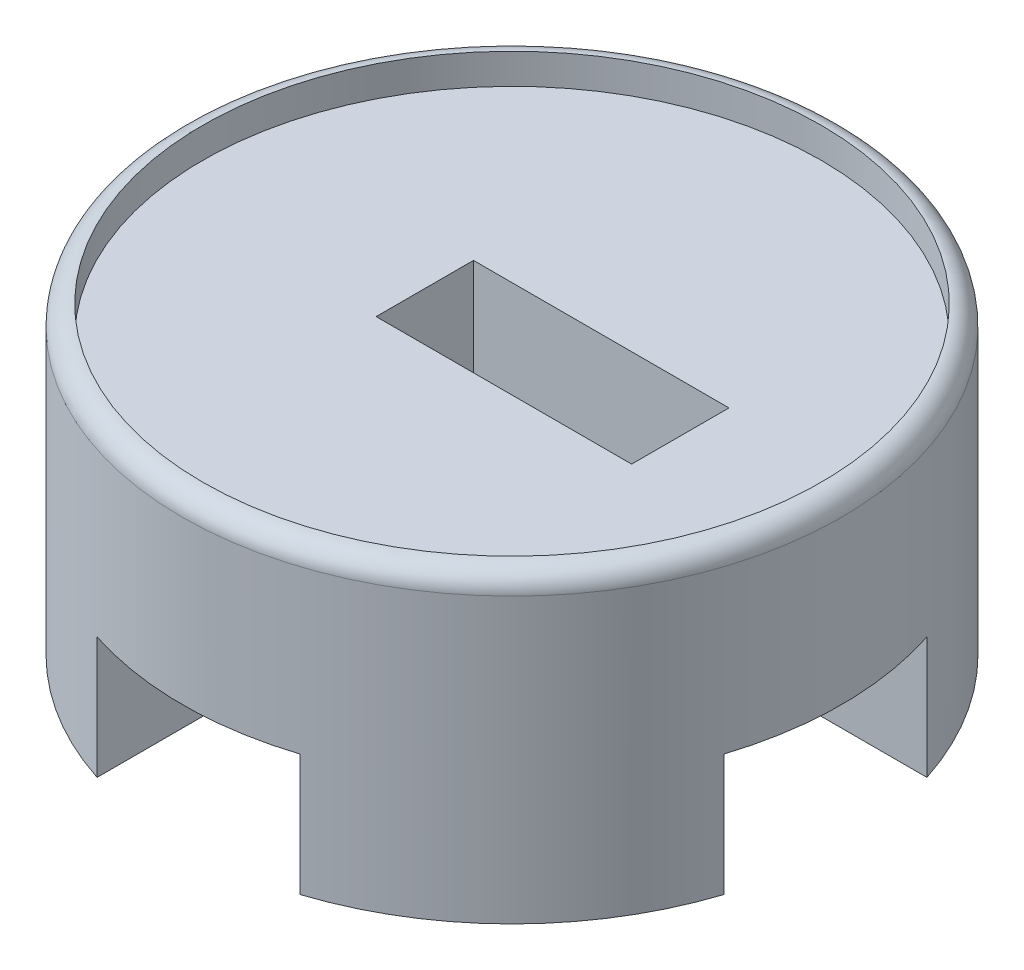
SolidWorks part; units mm, degrees
ref_plane "Front Plane" through (0, 0, 0) normal (0, 0, 1) x (1, 0, 0)
ref_plane "Top Plane" through (0, 0, 0) normal (0, 1, 0) x (1, 0, 0)
ref_plane "Right Plane" through (0, 0, 0) normal (1, 0, 0) x (0, 0, -1)
sketch "Sketch2" plane through (0, 0, 0) normal (0, 1, 0) x (1, 0, 0)
  circle A0 centre (0, 0) radius 41.275
  dimension "D1" = 82.55
extrude "Boss-Extrude2" add sketch "Sketch2" along normal blind 38.1
sketch "Sketch3" plane through (0, 38.1, 0) normal (0, 1, 0) x (1, 0, 0)
  circle A2 centre (0, 0) radius 38.735
  circle A3 centre (0, 0) radius 38.735
  dimension "D1" = 2.54
extrude "Cut-Extrude1" cut sketch "Sketch3" against normal blind 3.81
sketch "Sketch4" plane through (0, 0, 0) normal (0, -1, 0) x (1, 0, 0)
  line L1 (-12.7, -41.275) -> (12.7, -41.275)
  line L2 (-12.7, -41.275) -> (-12.7, 41.275)
  line L3 (-12.7, 41.275) -> (12.7, 41.275)
  line L4 (12.7, -41.275) -> (12.7, 41.275)
  line L5 (-12.7, -41.275) -> (12.7, 41.275) construction
  line L6 (-12.7, 41.275) -> (12.7, -41.275) construction
  line L7 (-41.275, 12.7) -> (41.275, 12.7)
  line L8 (-41.275, 12.7) -> (-41.275, -12.7)
  line L9 (-41.275, -12.7) -> (41.275, -12.7)
  line L10 (41.275, 12.7) -> (41.275, -12.7)
  line L11 (-41.275, 12.7) -> (41.275, -12.7) construction
  line L12 (-41.275, -12.7) -> (41.275, 12.7) construction
  circle A0 centre (0, 0) radius 41.275 construction
  point P0 (0, 0)
  point P6 (0, 0)
  point P11 (0, 41.275)
  point P14 (41.275, 0)
  circle M9 centre (0, 0) radius 41.275
  dimension "D1" = 25.4
extrude "Cut-Extrude2" cut sketch "Sketch4" against normal offset from surface (15.24 mm away) 19.05 contours L9 L2 L4 M9 | L2 L9 L4 L7 | L2 L7 L4 M9 | L4 L9 L7 M9 | L9 L2 L7 M9 region at (0, 0, -26.6634) region at (-26.6634, 0, 0) region at (0, 0, 0) region at (26.6634, 0, 0) region at (0, 0, 26.6634)
sketch "Sketch5" plane through (0, 34.29, 0) normal (0, 1, 0) x (1, 0, 0)
  line L1 (-10.922, -6.096) -> (21.082, -6.096)
  line L2 (-10.922, -6.096) -> (-10.922, 6.096)
  line L3 (-10.922, 6.096) -> (21.082, 6.096)
  line L4 (21.082, -6.096) -> (21.082, 6.096)
  circle A0 centre (0, 0) radius 2.54 construction
  point P7 (21.082, 0)
  dimension "D3" = 5.08
  dimension "D1" = 32.004
  dimension "D2" = 12.192
  dimension "D4" = 10.922
extrude "Cut-Extrude3" cut sketch "Sketch5" against normal blind 13.97
sketch "Sketch6" plane through (0, 20.32, 0) normal (0, 1, 0) x (1, 0, 0)
  line L1 (-6.223, -6.096) -> (16.383, -6.096)
  line L2 (-6.223, -6.096) -> (-6.223, 6.096)
  line L3 (-6.223, 6.096) -> (16.383, 6.096)
  line L4 (-10.922, 6.096) -> (-10.922, -6.096)
  line L5 (-10.922, -6.096) -> (21.082, -6.096)
  line L6 (21.082, -6.096) -> (21.082, 6.096)
  line L7 (21.082, 6.096) -> (-10.922, 6.096)
  line L8 (-10.922, 6.096) -> (-10.922, -6.096)
  line L9 (-10.922, -6.096) -> (21.082, -6.096)
  line L10 (21.082, -6.096) -> (21.082, 6.096)
  line L11 (21.082, 6.096) -> (-10.922, 6.096)
  line L12 (16.383, -6.096) -> (16.383, 6.096)
  point P10 (5.08, 6.096)
  point P11 (5.08, -6.096)
  line M10 (-10.922, -6.096) -> (21.082, -6.096)
  line M12 (21.082, 6.096) -> (-10.922, 6.096)
  dimension "D2" = 22.606
  dimension "D1" = 0
extrude "Cut-Extrude4" cut sketch "Sketch6" against normal through all contours L12 L2 M10 M12 region at (5.08, 20.32, 0)
fillet "Fillet1" radius 2.54 5 edges at (12.7, 7.62, -12.7) (0, 38.1, 41.275) (12.7, 7.62, 12.7) (-12.7, 7.62, 12.7) (-12.7, 7.62, -12.7)
